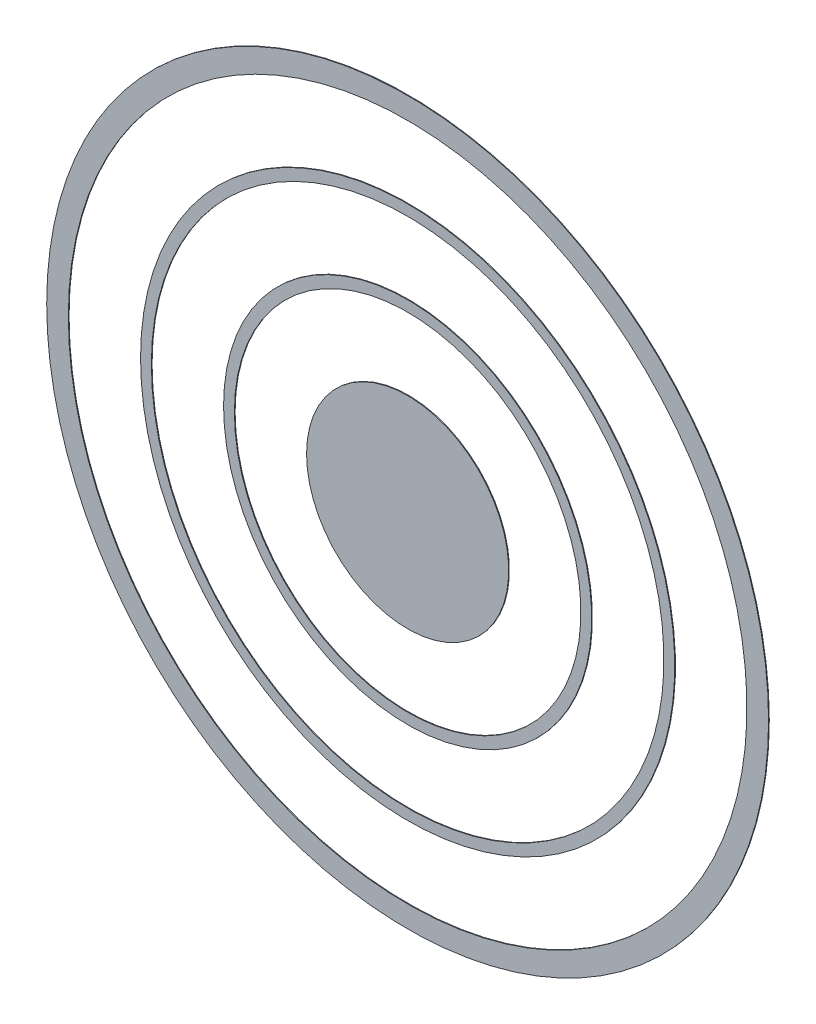
SolidWorks part; units mm, degrees
material "ABS"
ref_plane "Front" through (0, 0, 0) normal (0, 0, 1) x (1, 0, 0)
ref_plane "Top" through (0, 0, 0) normal (0, 1, 0) x (1, 0, 0)
ref_plane "Right" through (0, 0, 0) normal (1, 0, 0) x (0, 0, -1)
sketch "Эскиз1" plane through (0, 0, 0) normal (0, 0, 1) x (1, 0, 0)
  line L0 (0, 1.4) -> (0, 2.4) construction
  line L1 (0, 2.55) -> (0, 3.55) construction
  line L2 (0, 3.7) -> (0, 4.7) construction
  circle A0 centre (0, 0) radius 5
  circle A1 centre (0, 0) radius 4.7
  circle A2 centre (0, 0) radius 3.7
  circle A3 centre (0, 0) radius 3.55
  circle A4 centre (0, 0) radius 1.4
  circle A5 centre (0, 0) radius 2.4
  circle A6 centre (0, 0) radius 2.55
  dimension "D1" = 10
  dimension "D2" = 0.3
  dimension "D3" = 0.15
  dimension "D6" = 0.15
  dimension "D7" = 2.8
extrude "Бобышка-Вытянуть1" add sketch "Эскиз1" along normal blind 0.01 contours A0 A1 | A2 A3 | A6 A5 | A4 region at (-4.8586, 0, 0) region at (-3.5953, 0, 0) region at (0, 0, 0) region at (-2.4779, 0, 0)
sketch "Эскиз2" [suppressed] plane through (0, 0, 0) normal (0, 0, 1) x (1, 0, 0)
  text T0 "Touch\r\n  Key" font "Century Gothic" height 1.5
